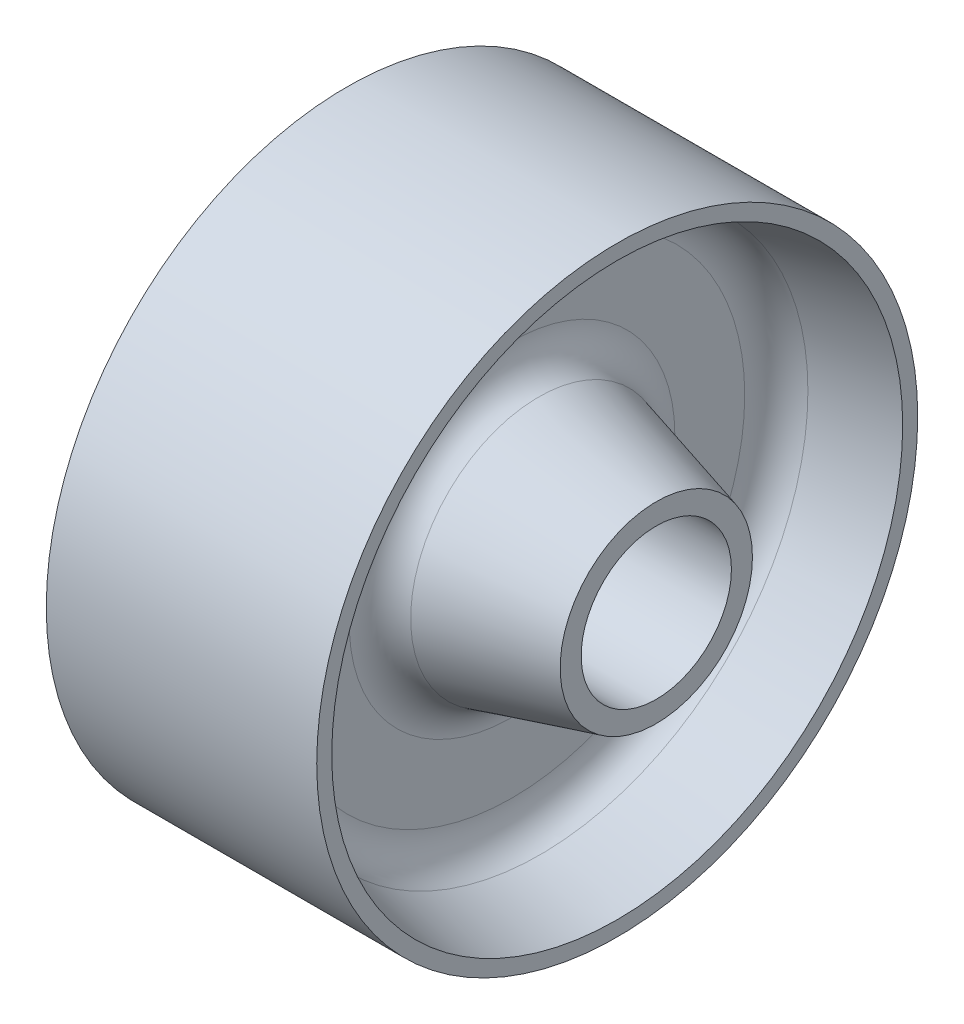
SolidWorks part; units mm, degrees
material "Gray Cast Iron"
ref_plane "Front Plane" through (0, 0, 0) normal (0, 0, 1) x (1, 0, 0)
ref_plane "Top Plane" through (0, 0, 0) normal (0, 1, 0) x (1, 0, 0)
ref_plane "Right Plane" through (0, 0, 0) normal (1, 0, 0) x (0, 0, -1)
sketch "Sketch3" plane through (0, 0, 0) normal (0, 1, 0) x (1, 0, 0)
  line L0 (0, 0) -> (0, 50) construction
  line L1 (0, 0) -> (-49.9743, 0) construction
  line L2 (-49.9743, 0) -> (74.5133, 0) construction
  line L3 (74.5133, 0) -> (0, 0) construction
  line L4 (29, 0) -> (-29, 0)
  line L5 (29, 0) -> (-29, 0)
  line L6 (-29, 0) -> (-29, 16)
  line L7 (-29, 16) -> (-9.4315, 21.2998)
  line L8 (-5, 27.0912) -> (-5, 38.7167)
  line L9 (-9.6631, 44.5658) -> (-22.5, 47.5)
  line L10 (-22.5, 47.5) -> (-22.5, 50)
  line L11 (-22.5, 50) -> (22.5, 50)
  line L12 (0, 50) -> (0, 0)
  line L13 (22.5, 47.5) -> (22.5, 50)
  line L14 (9.6631, 44.5658) -> (22.5, 47.5)
  line L15 (5, 27.0912) -> (5, 38.7167)
  line L16 (29, 16) -> (9.4315, 21.2998)
  line L17 (29, 0) -> (29, 16)
  arc A0 (5, 27.0912) -> (9.4315, 21.2998) centre (11, 27.0912) ccw
  arc A1 (9.6631, 44.5658) -> (5, 38.7167) centre (11, 38.7167) ccw
  arc A2 (-5, 38.7167) -> (-9.6631, 44.5658) centre (-11, 38.7167) ccw
  arc A3 (-9.4315, 21.2998) -> (-5, 27.0912) centre (-11, 27.0912) ccw
  point P21 (5, 22.5)
  point P24 (5, 43.5)
  point P27 (-5, 43.5)
  point P30 (-5, 22.5)
  dimension "D8" = 6
  dimension "D1" = 16
  dimension "D2" = 22.5
  dimension "D3" = 43.5
  dimension "D4" = 47.5
  dimension "D5" = 50
  dimension "D6" = 22.5
  dimension "D7" = 29
  dimension "D9" = 10
revolve "Revolve7" add sketch "Sketch3" angle 360 about L4 region at (11.509, 0, -18.4825) region at (-11.509, 0, -18.4825)
sketch3d "3DSketch5"
  line L0 (-29, -14.7876, -6.1096) -> (-29, 14.7876, 6.1096) construction
  line L1 (-29, -6.1096, 14.7876) -> (-29, 6.1096, -14.7876) construction
  circle A0 centre (-29, 0, 0) radius 16 construction
  circle A1 centre (-29, 0, 0) radius 12.5
  point P4 (-13, 0, 0)
  point P9 (-16.5, 0, 0)
  dimension "D1" = 25
extrude "Cut-Extrude1" cut sketch "3DSketch5" along direction (1, 0, 0) on the side of the normal blind 58
